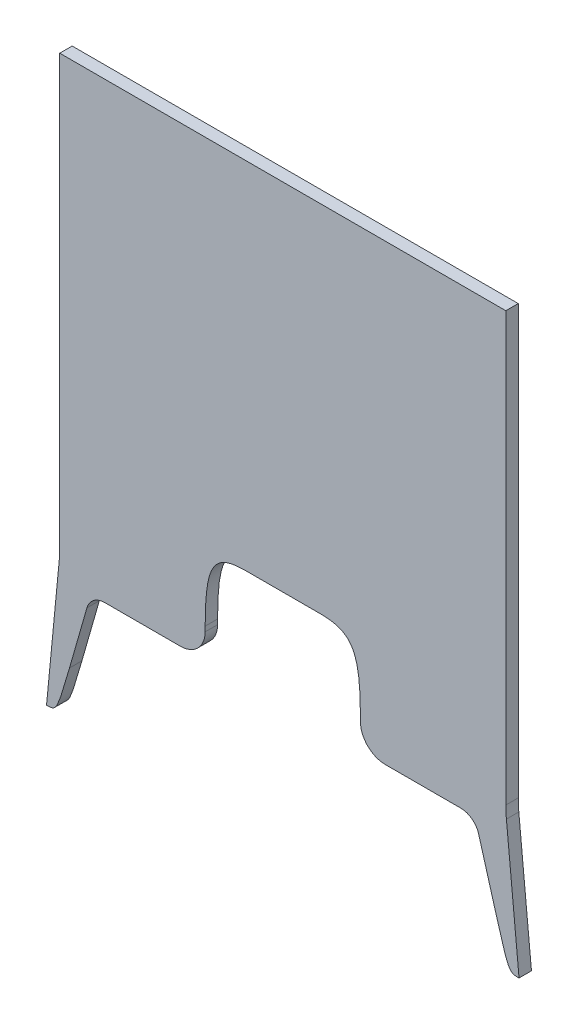
SolidWorks part; units mm, degrees
material "MDF"
ref_plane "Front Plane" through (0, 0, 0) normal (0, 0, 1) x (1, 0, 0)
ref_plane "Top Plane" through (0, 0, 0) normal (0, 1, 0) x (1, 0, 0)
ref_plane "Right Plane" through (0, 0, 0) normal (1, 0, 0) x (0, 0, -1)
sketch "Sketch1" plane through (0, 0, 0) normal (0, 0, 1) x (1, 0, 0)
  line L0 (-228.0888, 0) -> (228.0888, 0)
  line L1 (79.375, -363.22) -> (-79.375, -363.22)
  line L2 (0, -363.22) -> (0, 0) construction
  line L3 (-79.375, -363.22) -> (-79.375, -463.55)
  line L4 (196.3388, -463.55) -> (79.375, -463.55)
  line L5 (-230.9346, -584.2) -> (-196.3388, -463.55)
  line L6 (-230.9346, -584.2) -> (-241.6001, -584.2)
  line L7 (-241.6001, -584.2) -> (-228.0888, -443.879)
  line L8 (-228.0888, -443.879) -> (-228.0888, 0)
  line L9 (-196.3388, -463.55) -> (-79.375, -463.55)
  line L10 (228.0888, -443.879) -> (228.0888, 0)
  line L11 (241.6001, -584.2) -> (228.0888, -443.879)
  line L12 (230.9346, -584.2) -> (241.6001, -584.2)
  line L13 (230.9346, -584.2) -> (196.3388, -463.55)
  line L14 (79.375, -363.22) -> (79.375, -463.55)
  dimension "D1" = 363.22
  dimension "D2" = 158.75
  dimension "D3" = 106
  dimension "D4" = 31.75
  dimension "D5" = 120.65
  dimension "D6" = 174.5
  dimension "D7" = 463.55
  dimension "D8" = 140.97
extrude "Boss-Extrude1" add sketch "Sketch1" along normal blind 12.7
fillet "Fillet2" radius 69.85 1 edges at (-79.375, -363.22, 6.35) second distance 41.275 conic rho 0.6 first distance on face at (-79.375, -413.385, 6.35)
fillet "Fillet3" radius 25.4 1 edges at (-79.375, -463.55, 6.35)
fillet "Fillet4" radius 19.05 1 edges at (-196.3388, -463.55, 6.35)
ref_plane "Plane1" through (-230.9346, -584.2, 0) normal (0, 0, -1) x (-1, 0, 0)
fillet "Fillet5" radius 22.225 1 edges at (-230.9346, -584.2, 6.35) second distance 50.8 conic rho 0.7 first distance on face at (-236.2674, -584.2, 6.35)
fillet "Fillet6" radius 127 1 edges at (-228.0888, -443.879, 6.35)
sketch "Sketch3" plane through (0, 0, 12.7) normal (0, 0, 1) x (1, 0, 0)
  line L0 (0, 0) -> (0, -440.5951) construction
  line L2 (228.0888, 0) -> (-228.0888, 0) construction
  line L4 (0, 0) -> (241.6001, 0)
  line L5 (0, 0) -> (0, -584.2)
  line L6 (0, -584.2) -> (241.6001, -584.2)
  line L7 (241.6001, 0) -> (241.6001, -584.2)
  point P3 (0, 0)
extrude "Cut-Extrude1" cut sketch "Sketch3" against normal up to next
mirror "Mirror5" about plane through (0, 0, -0.3502) normal (-1, 0, 0) of bodies 103
